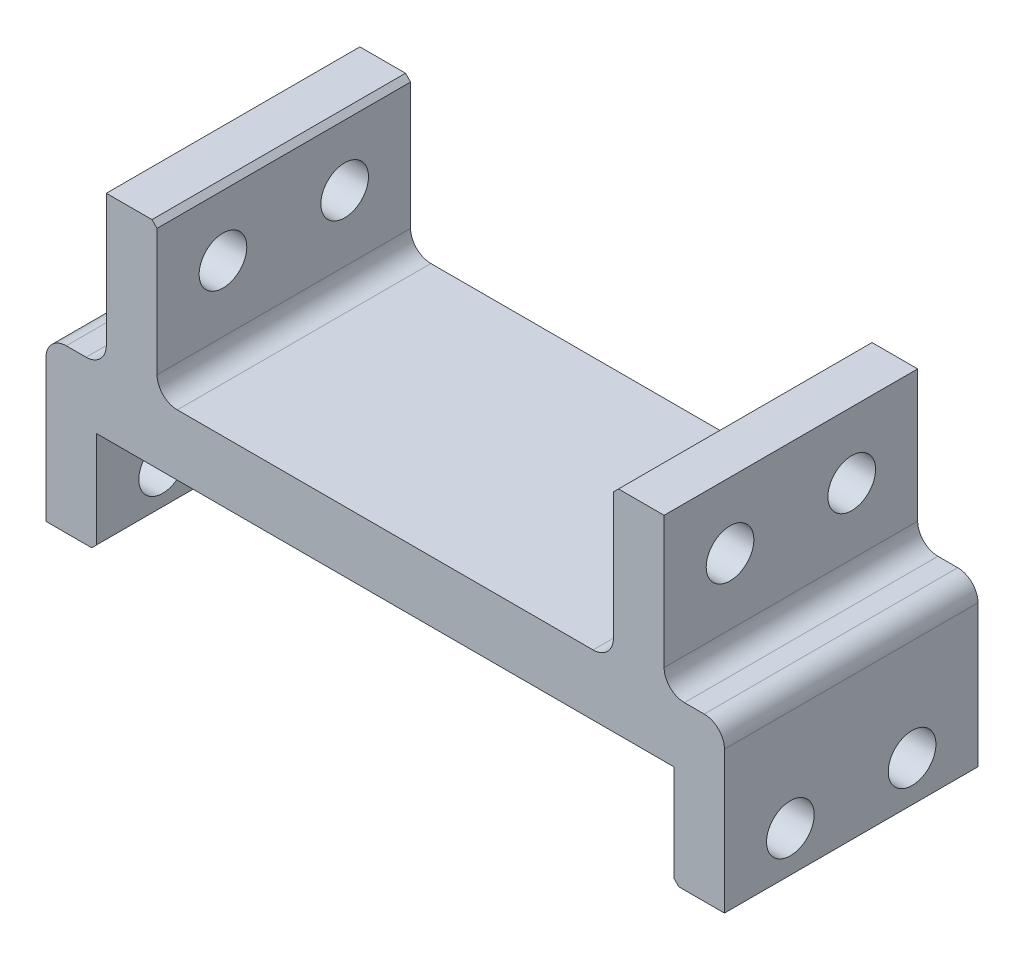
SolidWorks part; units mm, degrees
ref_plane "Front Plane" through (0, 0, 0) normal (0, 0, 1) x (1, 0, 0)
ref_plane "Top Plane" through (0, 0, 0) normal (0, 1, 0) x (1, 0, 0)
ref_plane "Right Plane" through (0, 0, 0) normal (1, 0, 0) x (0, 0, -1)
sketch "Sketch5" plane through (0, 0, 0) normal (0, 0, 1) x (1, 0, 0)
  line L0 (28.25, -2) -> (28.25, -43.5) construction
  line L1 (-26.25, 0) -> (26.25, 0) construction
  line L2 (-28.25, -43.5) -> (-28.25, -2) construction
  line L3 (28.25, 0) -> (28.25, -43.5) construction
  line L4 (-28.25, 0) -> (28.25, 0) construction
  line L5 (-28.25, -43.5) -> (-28.25, 0) construction
  line L6 (-28.45, -9.8) -> (-28.45, 0.2)
  line L7 (-28.45, 0.2) -> (28.45, 0.2)
  line L8 (28.45, 0.2) -> (28.45, -9.8)
  line L9 (-28.45, -43.5) -> (-28.45, 0.2) construction
  line L10 (28.45, 0.2) -> (28.45, -43.5) construction
  line L11 (0, 0.2) -> (0, -12.0605) construction
  line L13 (-28.45, -9.8) -> (-33.45, -9.8)
  line L14 (28.45, -9.8) -> (33.45, -9.8)
  line L15 (-33.45, -9.8) -> (-33.45, 4.2)
  line L16 (33.45, -9.8) -> (33.45, 4.2)
  line L17 (-31.45, 6.2) -> (-29.5, 6.2)
  line L18 (31.45, 6.2) -> (29.5, 6.2)
  line L19 (-27.5, 8.2) -> (-27.5, 21.2)
  line L20 (27.5, 8.2) -> (27.5, 21.2)
  line L21 (-27.5, 21.2) -> (-22.5, 21.2)
  line L22 (27.5, 21.2) -> (22.5, 21.2)
  line L23 (-22.5, 21.2) -> (-22.5, 8.2)
  line L24 (22.5, 21.2) -> (22.5, 8.2)
  line L25 (-20.5, 6.2) -> (20.5, 6.2)
  arc A0 (-22.5, 8.2) -> (-20.5, 6.2) centre (-20.5, 8.2) ccw
  arc A1 (22.5, 8.2) -> (20.5, 6.2) centre (20.5, 8.2) cw
  arc A2 (29.5, 6.2) -> (27.5, 8.2) centre (29.5, 8.2) cw
  arc A3 (33.45, 4.2) -> (31.45, 6.2) centre (31.45, 4.2) ccw
  arc A4 (-29.5, 6.2) -> (-27.5, 8.2) centre (-29.5, 8.2) ccw
  arc A5 (-33.45, 4.2) -> (-31.45, 6.2) centre (-31.45, 4.2) cw
  point P29 (28.922, -9.8)
  point P31 (-22.5, 6.2)
  point P34 (22.5, 6.2)
  point P37 (27.5, 6.2)
  point P40 (33.45, 6.2)
  point P43 (-27.5, 6.2)
  point P46 (-33.45, 6.2)
  dimension "D7" = 2
  dimension "D2" = 10
  dimension "D3" = 5
  dimension "D4" = 5
  dimension "D5" = 45
  dimension "D6" = 6
  dimension "D8" = 15
  dimension "D1" = 0.2
extrude "Boss-Extrude3" add sketch "Sketch5" along normal mid plane 25
sketch "Sketch6" plane through (0, 0, 0) normal (1, 0, 0) x (0, 0, -1)
  line L0 (-12.5, 8.2) -> (12.5, 8.2) construction
  line L1 (-6, 14.7) -> (6, 14.7) construction
  line L2 (-6, 14.7) -> (-6, -5.8) construction
  line L3 (-6, -5.8) -> (6, -5.8) construction
  line L4 (6, 14.7) -> (6, -5.8) construction
  line L5 (-6, 14.7) -> (6, -5.8) construction
  line L6 (-6, -5.8) -> (6, 14.7) construction
  line L7 (-12.5, 21.2) -> (12.5, 21.2) construction
  line L9 (-12.5, -9.8) -> (12.5, -9.8) construction
  circle A0 centre (-6, 14.7) radius 2.35
  circle A1 centre (6, 14.7) radius 2.35
  circle A2 centre (6, -5.8) radius 2.35
  circle A3 centre (-6, -5.8) radius 2.35
  point P6 (5.8749, 14.7891)
  point P8 (-6.4297, -5.4868)
  point P10 (0, 4.45)
  point P11 (6.6774, -5.6473)
  point P12 (0, 0)
  dimension "D1" = 4.7
  dimension "D2" = 12
  dimension "D3" = 4
extrude "Cut-Extrude1" cut sketch "Sketch6" against normal through all both and the other way through all
chamfer "Chamfer1" distance 0.5 angle 45 4 edges at (22.5, 21.2, 0) (-22.5, 21.2, 0) (28.45, -9.8, 0) (-28.45, -9.8, 0)
